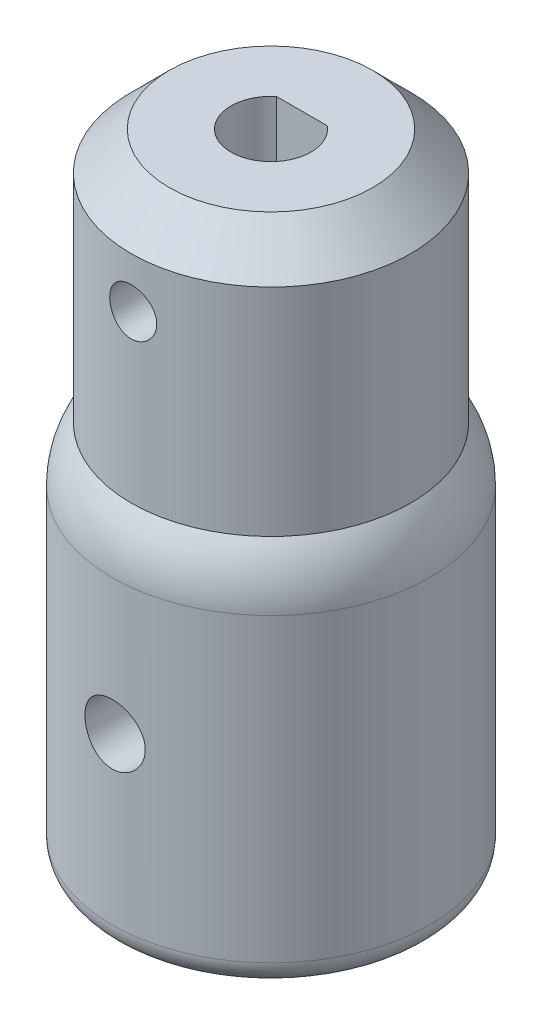
SolidWorks part; units mm, degrees
ref_plane "Front Plane" through (0, 0, 0) normal (0, 0, 1) x (1, 0, 0)
ref_plane "Top Plane" through (0, 0, 0) normal (0, 1, 0) x (1, 0, 0)
ref_plane "Right Plane" through (0, 0, 0) normal (1, 0, 0) x (0, 0, -1)
sketch "Sketch1" plane through (0, 0, 0) normal (0, 1, 0) x (1, 0, 0)
  line L0 (-2, 2.4336) -> (2, 2.4336)
  circle A0 centre (0, 0) radius 11
  circle A1 centre (0, 0) radius 7.7
  circle A2 centre (0, 0) radius 3.15
  circle A3 centre (0, 0) radius 12.5
  dimension "D1" = 22
  dimension "D2" = 15.4
  dimension "D3" = 6.3
  dimension "D5" = 25
  dimension "D4" = 4
extrude "Boss-Extrude1" add sketch "Sketch1" along normal blind 30 contours A0 A1 region at (-10.6889, 0, 0)
extrude "Boss-Extrude2" add sketch "Sketch1<2>" along normal blind 5 from surface contours A1 | A0 A1 | L0 A2 | L0 A2 region at (0, 0, -2.7232) region at (0, 0, 0.1826) region at (-10.6889, 0, 0) region at (-7.4822, 0, 0) starting at face at (0, 30, 7.7)
sketch "Sketch1<2>" plane through (0, 0, 0) normal (0, 1, 0) x (1, 0, 0) same geometry as "Sketch1"
extrude "Boss-Extrude3" add sketch "Sketch1<4>" along normal blind 15 from surface contours A0 A1 | A1 A2 | L0 A2 region at (0, 0, -2.7232) region at (-10.6889, 0, 0) region at (-7.4822, 0, 0) starting at face at (0, 35, 11)
sketch "Sketch1<4>" plane through (0, 0, 0) normal (0, 1, 0) x (1, 0, 0) same geometry as "Sketch1"
extrude "Boss-Extrude4" add sketch "Sketch1<5>" along normal up to surface (30 mm away) contours A3 A0 region at (-12.1464, 0, 0) up to face at (0, 30, 7.7)
sketch "Sketch1<5>" plane through (0, 0, 0) normal (0, 1, 0) x (1, 0, 0) same geometry as "Sketch1"
ref_plane "Plane1" through (0, 0, -12.5) normal (0, 0, -1) x (-1, 0, 0)
sketch "Sketch2" plane through (0, 0, -12.5) normal (0, 0, -1) x (-1, 0, 0)
  line L0 (-11, 0) -> (11, 0) construction
  line L1 (11, 50) -> (-11, 50) construction
  line L2 (-11, 0) -> (11, 0)
  line L3 (11, 50) -> (-11, 50)
  line L5 (4.2147, 15) -> (2.1073, 18.65)
  line L6 (2.1073, 18.65) -> (-2.1073, 18.65)
  line L7 (-2.1073, 18.65) -> (-4.2147, 15)
  line L8 (-4.2147, 15) -> (-2.1073, 11.35)
  line L9 (-2.1073, 11.35) -> (2.1073, 11.35)
  line L10 (2.1073, 11.35) -> (4.2147, 15)
  circle A0 centre (0, 43.0422) radius 1.85
  circle A1 centre (0, 15) radius 3.65 construction
  circle A2 centre (0, 15) radius 2.3716
  dimension "D1" = 3.7
  dimension "D3" = 7.3
  dimension "D5" = 4.7432
  dimension "D2" = 6.9578
  dimension "D4" = 15
extrude "Cut-Extrude1" cut sketch "Sketch2" against normal through all contours A0 region at (0, 43.0422, -12.5)
extrude "Cut-Extrude2" cut sketch "Sketch2<7>" against normal blind 4 contours L9 L10 L5 L6 L7 L8 A2 | A2 region at (-3.0644, 13.2308, -12.5) region at (0, 15, -12.5)
sketch "Sketch2<7>" plane through (0, 0, -12.5) normal (0, 0, -1) x (-1, 0, 0) same geometry as "Sketch2"
extrude "Cut-Extrude3" cut sketch "Sketch2<8>" against normal through all contours A2 region at (0, 15, -12.5)
sketch "Sketch2<8>" plane through (0, 0, -12.5) normal (0, 0, -1) x (-1, 0, 0) same geometry as "Sketch2"
fillet "Fillet1" radius 7 1 edges at (0, 30, 12.5)
fillet "Fillet2" radius 2 2 edges at (0, 0, 7.7) (0, 0, 12.5)
chamfer "Chamfer1" distance 3 angle 45 1 edges at (0, 50, 11)
